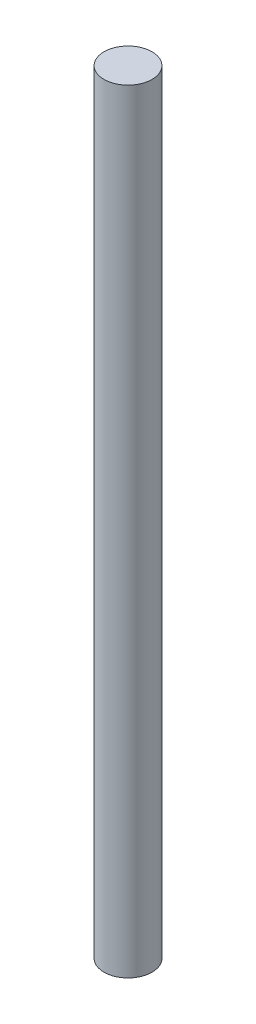
SolidWorks part; units mm, degrees
ref_plane "Front Plane" through (0, 0, 0) normal (0, 0, 1) x (1, 0, 0)
ref_plane "Top Plane" through (0, 0, 0) normal (0, 1, 0) x (1, 0, 0)
ref_plane "Right Plane" through (0, 0, 0) normal (1, 0, 0) x (0, 0, -1)
sketch "Sketch2" plane through (0, 0, 0) normal (0, 1, 0) x (1, 0, 0)
  circle A0 centre (0, 0) radius 1.8
  dimension "D1" = 3.6
extrude "Boss-Extrude1" add sketch "Sketch2" along normal blind 58
